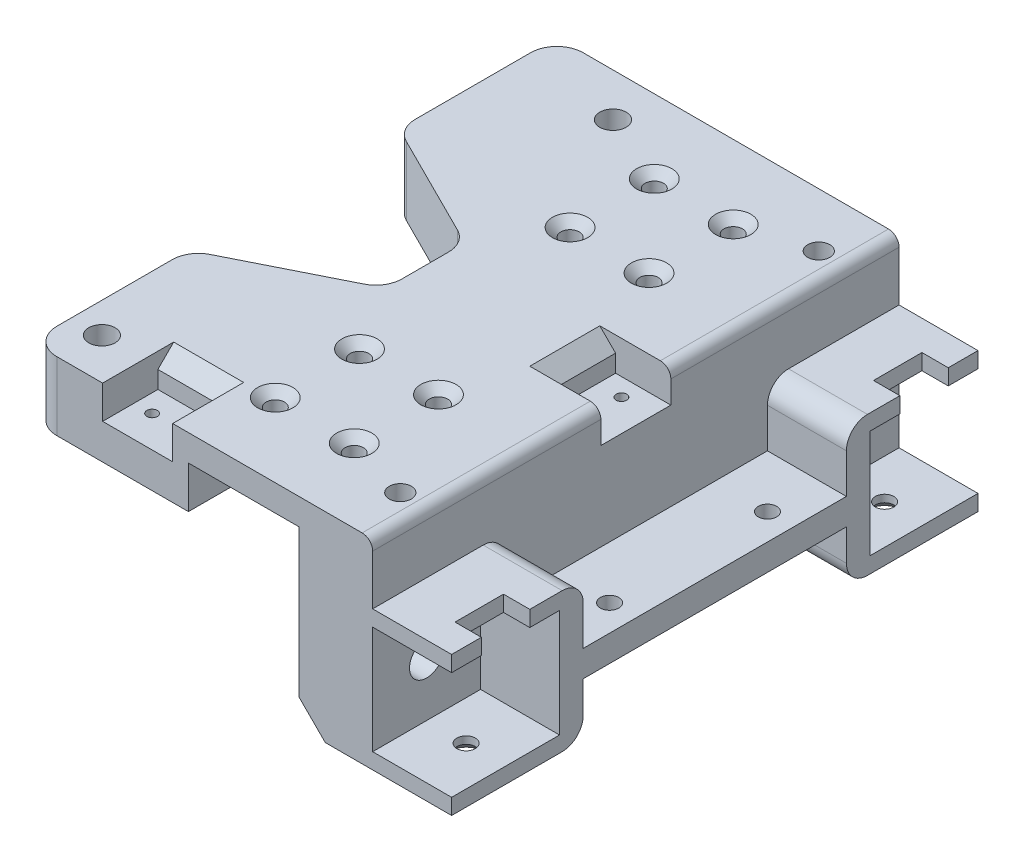
SolidWorks part; units mm, degrees
ref_plane "Front Plane" through (0, 0, 0) normal (0, 0, 1) x (1, 0, 0)
ref_plane "Top Plane" through (0, 0, 0) normal (0, 1, 0) x (1, 0, 0)
ref_plane "Right Plane" through (0, 0, 0) normal (1, 0, 0) x (0, 0, -1)
sketch "Sketch1" plane through (0, 0, 0) normal (0, 1, 0) x (1, 0, 0)
  line L0 (0, 50) -> (0, -50) construction
  line L1 (-10, 50) -> (10, 50)
  line L2 (-10, 50) -> (-10, -50)
  line L3 (-10, -50) -> (10, -50)
  line L4 (10, 50) -> (10, -50) construction
  line L5 (-10, 50) -> (10, -50) construction
  line L6 (-10, -50) -> (10, 50) construction
  line L7 (-7.5, 36) -> (7.5, 36) construction
  line L8 (-7.5, 36) -> (7.5, 20) construction
  line L9 (-10, 0) -> (10, 0) construction
  line L10 (-7.5, -36) -> (7.5, -20) construction
  line L11 (-7.5, -36) -> (7.5, -36) construction
  line L12 (-7.5, 20) -> (7.5, 20) construction
  line L13 (10, 50) -> (11, 50)
  line L14 (11, 50) -> (11, -50)
  line L15 (11, -50) -> (10, -50)
  circle A0 centre (-7.5, 36) radius 1.75
  circle A1 centre (7.5, 36) radius 1.75
  circle A2 centre (-7.5, 20) radius 1.75
  circle A3 centre (7.5, 20) radius 1.75
  circle A4 centre (7.5, -20) radius 1.75
  circle A5 centre (-7.5, -20) radius 1.75
  circle A6 centre (7.5, -36) radius 1.75
  circle A7 centre (-7.5, -36) radius 1.75
  point P0 (0, 0)
  point P16 (0, 36)
  dimension "D2" = 3.5
  dimension "D1" = 20
  dimension "D3" = 15
  dimension "D4" = 16
  dimension "D5" = 100
  dimension "D6" = 20
  dimension "D7" = 1
extrude "Boss-Extrude1" add sketch "Sketch1" along normal blind 5
sketch "Sketch2" plane through (11, 0, 0) normal (1, 0, 0) x (0, 0, -1)
  line L1 (-50, 5) -> (50, 5)
  line L2 (-50, 5) -> (-50, -33)
  line L3 (-50, -33) -> (50, -33)
  line L5 (50, 5) -> (50, -33)
  line L6 (50, 5) -> (50, 0) construction
  line L7 (-50, 5) -> (-50, 0) construction
  line L8 (-50, 5) -> (50, 5) construction
  dimension "D1" = 38
extrude "Boss-Extrude2" add sketch "Sketch2" along normal blind 14
sketch "Sketch3" plane through (25, 0, 0) normal (1, 0, 0) x (0, 0, -1)
  line L0 (0, 5) -> (0, -33) construction
  line L1 (-25, -18) -> (25, -18)
  line L2 (-25, -18) -> (-25, -23)
  line L3 (-25, -23) -> (25, -23)
  line L4 (25, -18) -> (25, -23)
  line L5 (50, 5) -> (-50, 5) construction
  line L6 (-50, -33) -> (50, -33) construction
  point P10 (0, -18)
  dimension "D1" = 5
  dimension "D2" = 50
  dimension "D3" = 10
extrude "Boss-Extrude3" add sketch "Sketch3" along normal blind 15
sketch "Sketch4" plane through (0, -18, 0) normal (0, 1, 0) x (1, 0, 0)
  line L0 (30, 0) -> (40, 0) construction
  line L2 (40, 25) -> (40, -25) construction
  line L3 (35, -15) -> (35, 15) construction
  circle A0 centre (35, 15) radius 1.75
  circle A1 centre (35, -15) radius 1.75
  point P8 (35, 0)
  dimension "D1" = 30
  dimension "D2" = 3.5
  dimension "D3" = 10
extrude "Cut-Extrude1" cut sketch "Sketch4" against normal through all
sketch "Sketch8" plane through (25, 0, 0) normal (1, 0, 0) x (0, 0, -1)
  line L0 (-50, 5) -> (-50, -33) construction
  line L1 (-50, -6.5) -> (-25, -6.5)
  line L2 (-50, -6.5) -> (-50, -9.5)
  line L3 (-50, -33) -> (-25, -33)
  line L4 (-25, -6.5) -> (-25, -33)
  line L5 (-50, -30) -> (-50, -33)
  line L6 (-50, -30) -> (-29.5, -30)
  line L8 (-50, -9.5) -> (-29.5, -9.5)
  line L9 (-29.5, -30) -> (-29.5, -9.5)
  line L10 (0, 20.9) -> (0, -20.9) construction
  line L11 (29.5, -30) -> (29.5, -9.5)
  line L12 (50, -9.5) -> (29.5, -9.5)
  line L13 (50, -30) -> (29.5, -30)
  line L14 (50, -30) -> (50, -33)
  line L15 (25, -6.5) -> (25, -33)
  line L16 (50, -33) -> (25, -33)
  line L17 (50, -6.5) -> (50, -9.5)
  line L18 (50, -6.5) -> (25, -6.5)
  line L19 (-50, -33) -> (50, -33) construction
  line L20 (-25, -18) -> (-25, -23) construction
  dimension "D1" = 3
  dimension "D3" = 3
  dimension "D4" = 20.5
  dimension "D5" = 20.5
extrude "Boss-Extrude6" add sketch "Sketch8" along normal blind 15
sketch "Sketch9" plane through (25, 0, 0) normal (1, 0, 0) x (0, 0, -1)
  line L0 (-50, -9.5) -> (-29.5, -30) construction
  line L1 (50, -9.5) -> (29.5, -30) construction
  circle A0 centre (-39.75, -19.75) radius 3.25
  circle A1 centre (39.75, -19.75) radius 3.25
  dimension "D1" = 6.5
extrude "Cut-Extrude3" cut sketch "Sketch9" against normal through all
sketch "Sketch10" plane through (11, 0, 0) normal (-1, 0, 0) x (0, 0, 1)
  circle A0 centre (-39.75, -19.75) radius 5.25
  circle A1 centre (39.75, -19.75) radius 5.25
  dimension "D1" = 10.5
extrude "Cut-Extrude4" cut sketch "Sketch10" against normal offset from surface (9 mm away) 5 up to face at (25, -19.75, 36.5)
sketch "Sketch11" plane through (0, -6.5, 0) normal (0, 1, 0) x (1, 0, 0)
  line L0 (40, -25) -> (40, -50) construction
  line L1 (40, -35.15) -> (35, -35.15)
  line L2 (40, -35.15) -> (40, -44.35)
  line L3 (40, -44.35) -> (35, -44.35)
  line L4 (35, -35.15) -> (35, -44.35)
  line L5 (35, -39.75) -> (40, -39.75) construction
  line L7 (-10, 0) -> (40, 0) construction
  line L8 (-10, 50) -> (-10, -50) construction
  line L9 (40, 25) -> (40, -25) construction
  line L10 (40, -35.15) -> (35, -35.15)
  line L11 (40, -44.35) -> (35, -44.35)
  line L12 (35, 39.75) -> (40, 39.75) construction
  line L13 (40, 44.35) -> (35, 44.35)
  line L14 (40, 35.15) -> (35, 35.15)
  line L15 (35, 35.15) -> (35, 44.35)
  line L16 (40, 44.35) -> (35, 44.35)
  line L17 (40, 35.15) -> (40, 44.35)
  line L18 (40, 35.15) -> (35, 35.15)
  line L19 (40, -50) -> (40, -29.5) construction
  point P22 (40, -39.75)
  line M7 (40, -50) -> (40, -25)
  dimension "D1" = 9.2
  dimension "D3" = 5
extrude "Cut-Extrude5" cut sketch "Sketch11" against normal up to next contours L1 L4 L3 M7 | L14 L17 L13 L15 region at (37.5, -6.5, 39.75) region at (37.5, -6.5, -39.75)
sketch "Sketch12" plane through (0, -30, 0) normal (0, 1, 0) x (1, 0, 0)
  line L0 (40, -39.75) -> (25, -39.75) construction
  line L1 (40, -29.5) -> (40, -50) construction
  line L2 (25, -25) -> (25, -50) construction
  line L3 (-20.9, 0) -> (20.9, 0) construction
  circle A0 centre (32.5, -39.75) radius 1.75
  circle A2 centre (32.5, 39.75) radius 1.75
  dimension "D1" = 3.5
extrude "Cut-Extrude6" cut sketch "Sketch12" against normal through all
sketch "Sketch13" plane through (-10, 0, 0) normal (-1, 0, 0) x (0, 0, 1)
  line L1 (-50, 5) -> (50, 5)
  line L2 (-50, 5) -> (-50, -8)
  line L3 (-50, -8) -> (50, -8)
  line L4 (50, 5) -> (50, -8)
  dimension "D1" = 13
extrude "Boss-Extrude7" add sketch "Sketch13" along normal blind 30
sketch "Sketch14" plane through (0, 5, 0) normal (0, 1, 0) x (1, 0, 0)
  line L0 (40, -25) -> (40, -35.15) construction
  line L6 (-27.8075, 41.8075) -> (-27.8075, -42.205) construction
  line L7 (40, -35.15) -> (35, -35.15) construction
  line L12 (-21.15, 35.15) -> (40, 35.15) construction
  line L18 (-34.2325, -35.78) -> (40, -35.78) construction
  circle A0 centre (-21.15, 41.8075) radius 2.5
  circle A1 centre (-34.2325, -42.205) radius 2.5
  circle A2 centre (-34.2325, -42.205) radius 6.425 construction
  circle A3 centre (-21.15, 41.8075) radius 6.6575 construction
  point P12 (0, 0)
  dimension "D1" = 5
  dimension "D2" = 5
  dimension "D4" = 12.85
  dimension "D5" = 13.315
  dimension "D6" = 0.63
  dimension "D3" = 21.15
extrude "Cut-Extrude7" cut sketch "Sketch14" against normal through all
sketch "Sketch15" plane through (0, -8, 0) normal (0, -1, 0) x (1, 0, 0)
  line L0 (-40, -50) -> (-40, 50) construction
  line L1 (-30.1325, 44.5721) -> (-34.2325, 46.9393)
  line L2 (-34.2325, 46.9393) -> (-38.3325, 44.5721)
  line L3 (-38.3325, 44.5721) -> (-38.3325, 39.8379)
  line L4 (-38.3325, 39.8379) -> (-34.2325, 37.4707)
  line L5 (-34.2325, 37.4707) -> (-30.1325, 39.8379)
  line L6 (-30.1325, 39.8379) -> (-30.1325, 44.5721)
  line L7 (-17.05, -44.1746) -> (-17.05, -39.4404)
  line L8 (-17.05, -39.4404) -> (-21.15, -37.0732)
  line L9 (-21.15, -37.0732) -> (-25.25, -39.4404)
  line L10 (-25.25, -39.4404) -> (-25.25, -44.1746)
  line L11 (-25.25, -44.1746) -> (-21.15, -46.5418)
  line L12 (-21.15, -46.5418) -> (-17.05, -44.1746)
  circle A0 centre (-34.2325, 42.205) radius 4.1 construction
  circle A1 centre (-21.15, -41.8075) radius 4.1 construction
  dimension "D1" = 8.2
extrude "Cut-Extrude8" cut sketch "Sketch15" against normal blind 5
sketch "Sketch16" plane through (0, 5, 0) normal (0, 1, 0) x (1, 0, 0)
  line L0 (20, 39.75) -> (40, 39.75) construction
  line L1 (40, 39.75) -> (40, -39.75) construction
  line L2 (40, -39.75) -> (20, -39.75) construction
  line L3 (20, -39.75) -> (20, 39.75) construction
  line L4 (40, 50) -> (40, 29.5) construction
  line L5 (40, -29.5) -> (40, -50) construction
  circle A0 centre (20, 39.75) radius 2.1
  circle A1 centre (20, -39.75) radius 2.1
  dimension "D1" = 4.2
  dimension "D2" = 4.2
  dimension "D3" = 20
extrude "Cut-Extrude9" cut sketch "Sketch16" against normal blind 4
chamfer "Chamfer1" distance 1.6 angle 45 8 edges at (7.5, 5, 34.25) (-7.5, 5, 34.25) (7.5, 5, 18.25) (-7.5, 5, 18.25) (7.5, 5, -18.25) (-7.5, 5, -18.25) (7.5, 5, -34.25) (-7.5, 5, -34.25)
sketch "Sketch17" plane through (0, 5, 0) normal (0, 1, 0) x (1, 0, 0)
  line L0 (-40, 20) -> (-15, 7.5)
  line L1 (-40, -50) -> (-40, 50) construction
  line L2 (-15, 7.5) -> (-15, -7.5)
  line L3 (-15, -7.5) -> (-40, -20)
  line L4 (-40, -20) -> (-40, 20)
  point P5 (-15, 0)
  dimension "D1" = 15
  dimension "D2" = 25
  dimension "D3" = 40
extrude "Cut-Extrude10" cut sketch "Sketch17" against normal through all
chamfer "Chamfer2" distance 1.6 angle 45 2 edges at (32.5, -33, -41.5) (32.5, -33, 41.5)
chamfer "Chamfer3" distance 5 angle 45 1 edges at (11, -33, 0)
sketch "Sketch18" plane through (0, 1, 0) normal (0, 1, 0) x (1, 0, 0)
  circle A0 centre (20, 39.75) radius 1.75
  circle A1 centre (20, -39.75) radius 1.75
  dimension "D1" = 3.5
  dimension "D2" = 3.5
extrude "Cut-Extrude11" cut sketch "Sketch18" against normal blind 4
fillet "Fillet1" radius 5 6 edges at (-40, -1.5, 50) (-40, -1.5, 20) (-15, -1.5, 7.5) (-15, -1.5, -7.5) (-40, -1.5, -20) (-40, -1.5, -50)
fillet "Fillet2" radius 4 4 edges at (32.5, -33, -25) (32.5, -6.5, -25) (32.5, -33, 25) (32.5, -6.5, 25)
sketch "Sketch19" plane through (25, 0, 0) normal (1, 0, 0) x (0, 0, -1)
  line L0 (50, 5) -> (-50, 5) construction
  line L1 (-6.65, 5) -> (6.65, 5)
  line L2 (-6.65, 5) -> (-6.65, -1.3)
  line L3 (-6.65, -1.3) -> (6.65, -1.3)
  line L4 (6.65, 5) -> (6.65, -1.3)
  point P7 (0, 5)
  dimension "D1" = 13.3
  dimension "D2" = 6.3
extrude "Cut-Extrude12" cut sketch "Sketch19" against normal blind 10.5
sketch "Sketch20" plane through (0, -1.3, 0) normal (0, 1, 0) x (1, 0, 0)
  line L0 (19, 3.25) -> (19, -3.25) construction
  line L3 (14.5, 6.65) -> (14.5, -6.65) construction
  line L4 (18, 3.25) -> (18, -3.25) construction
  circle A0 centre (19, 3.25) radius 1
  circle A1 centre (19, -3.25) radius 1
  point P2 (14.5, 0)
  point P3 (19, 0)
  dimension "D1" = 2
  dimension "D2" = 6.5
  dimension "D3" = 3.5
extrude "Cut-Extrude13" cut sketch "Sketch20" against normal blind 3
chamfer "Chamfer4" distance 3 angle 45 1 edges at (14.5, 5, 0)
fillet "Fillet3" radius 2 2 edges at (25, 5, -28.325) (25, 5, 28.325)
sketch "Sketch22" plane through (0, 5, 0) normal (0, 1, 0) x (1, 0, 0)
  line L0 (-35, -50) -> (23, -50) construction
  line L1 (-26.3, -50) -> (-13, -50)
  line L2 (-26.3, -50) -> (-26.3, -39.5)
  line L3 (-26.3, -39.5) -> (-13, -39.5)
  line L4 (-13, -50) -> (-13, -39.5)
  line L5 (-10, 50) -> (-10, -50) construction
  dimension "D1" = 10.5
  dimension "D2" = 13.3
  dimension "D3" = 3
extrude "Cut-Extrude14" cut sketch "Sketch22" against normal blind 6.3
sketch "Sketch23" plane through (0, -1.3, 0) normal (0, 1, 0) x (1, 0, 0)
  line L0 (-22.9, -44) -> (-16.4, -44) construction
  line L2 (-26.3, -50) -> (-13, -50) construction
  line L3 (-22.9, -43) -> (-16.4, -43) construction
  line L4 (-13, -39.5) -> (-26.3, -39.5) construction
  circle A0 centre (-22.9, -44) radius 1
  circle A1 centre (-16.4, -44) radius 1
  point P9 (-19.65, -50)
  point P10 (-19.65, -44)
  dimension "D1" = 2
  dimension "D2" = 2
  dimension "D3" = 6.5
  dimension "D4" = 3.5
extrude "Cut-Extrude15" cut sketch "Sketch23" against normal blind 3
chamfer "Chamfer5" distance 3 angle 45 1 edges at (-19.65, 5, 39.5)
